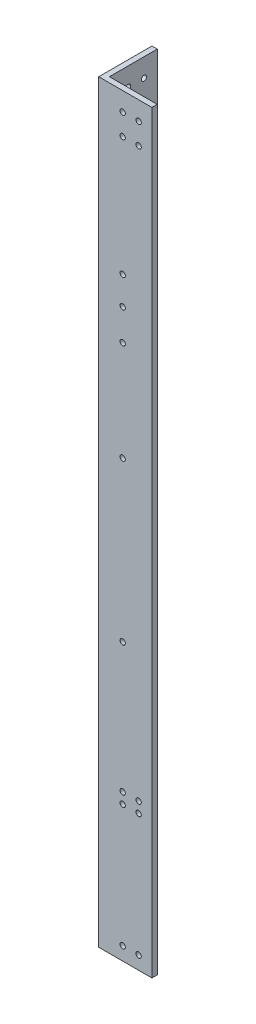
SolidWorks part; units mm, degrees
ref_plane "Front Plane" through (0, 0, 0) normal (0, 0, 1) x (1, 0, 0)
ref_plane "Top Plane" through (0, 0, 0) normal (0, 1, 0) x (1, 0, 0)
ref_plane "Right Plane" through (0, 0, 0) normal (1, 0, 0) x (0, 0, -1)
sketch "Sketch2" plane through (0, 0, 0) normal (0, 1, 0) x (1, 0, 0)
  line L0 (0, 31.75) -> (3.175, 31.75)
  line L1 (3.175, 31.75) -> (3.175, 3.175)
  line L2 (3.175, 3.175) -> (31.75, 3.175)
  line L3 (31.75, 3.175) -> (31.75, 0)
  line L4 (31.75, 0) -> (0, 0)
  line L5 (0, 0) -> (0, 31.75)
  point P9 (1.5875, 31.75)
  point P10 (31.75, 1.5875)
  dimension "D4" = 3.175
  dimension "D1" = 31.75
  dimension "D2" = 31.75
  dimension "D3" = 3.175
extrude "Boss-Extrude1" add sketch "Sketch2" along normal blind 450
sketch "FrontSideHoles-Sketch3" plane through (0, 0, 0) normal (0, 0, 1) x (1, 0, 0)
  line L0 (0, 0) -> (31.75, 0) construction
  line L3 (0, 450) -> (0, 0) construction
  circle A0 centre (14.2875, 81.1125) radius 1.5875
  circle A1 centre (23.8125, 81.1125) radius 1.5875
  circle A2 centre (14.2875, 87.4625) radius 1.5875
  circle A3 centre (23.8125, 87.4625) radius 1.5875
  circle A4 centre (14.2875, 438.8875) radius 1.5875
  circle A5 centre (14.2875, 426.1875) radius 1.5875
  circle A6 centre (23.8125, 438.8875) radius 1.5875
  circle A7 centre (23.8125, 426.1875) radius 1.5875
  circle A8 centre (14.2875, 338.1776) radius 1.5875
  circle A9 centre (14.2875, 319.6526) radius 1.5875
  circle A10 centre (14.2875, 260) radius 1.5875
  circle A11 centre (14.2875, 165) radius 1.5875
  circle A12 centre (14.2875, 355) radius 1.5875
  circle A13 centre (14.2875, 7.9375) radius 1.5875
  circle A14 centre (23.8125, 7.9375) radius 1.5875
  dimension "D4" = 3.175
  dimension "D1" = 81.1125
  dimension "D2" = 14.2875
  dimension "D8" = 11.1125
  dimension "D11" = 18.525
  dimension "D5" = 6.35
  dimension "D3" = 9.525
  dimension "D7" = 12.7
  dimension "D9" = 319.6526
  dimension "D6" = 165
  dimension "D10" = 95
  dimension "D13" = 95
  dimension "D12" = 7.9375
sketch "LeftSideHoles-Sketch4" plane through (0, 0, 0) normal (-1, 0, 0) x (0, 0, 1)
  line L0 (-31.75, 450) -> (0, 450) construction
  line L1 (0, 450) -> (0, 0) construction
  line L3 (-31.75, 0) -> (0, 0) construction
  circle A0 centre (-23.8125, 81.1125) radius 1.5875
  circle A1 centre (-14.2875, 81.1125) radius 1.5875
  circle A2 centre (-23.8125, 87.4625) radius 1.5875
  circle A3 centre (-14.2875, 87.4625) radius 1.5875
  circle A4 centre (-23.8125, 438.8875) radius 1.5875
  circle A5 centre (-14.2875, 438.8875) radius 1.5875
  circle A6 centre (-23.8125, 426.1875) radius 1.5875
  circle A7 centre (-14.2875, 426.1875) radius 1.5875
  circle A8 centre (-23.8125, 332.6026) radius 1.5875
  circle A9 centre (-14.2875, 332.6026) radius 1.5875
  circle A10 centre (-23.8125, 319.9026) radius 1.5875
  circle A11 centre (-14.2875, 319.9026) radius 1.5875
  circle A12 centre (-23.8125, 7.9375) radius 1.5875
  circle A13 centre (-14.2875, 7.9375) radius 1.5875
  circle A14 centre (-14.2875, 165) radius 7.0254
  circle A15 centre (-14.2875, 260) radius 7.1716
  circle A16 centre (-14.2875, 355) radius 6.6199
  dimension "D4" = 3.175
  dimension "D2" = 14.2875
  dimension "D7" = 12.7
  dimension "D13" = 95
  dimension "D3" = 81.1125
  dimension "D6" = 11.1125
  dimension "D5" = 6.35
  dimension "D10" = 7.9375
  dimension "D9" = 12.7
  dimension "D11" = 9.525
  dimension "D8" = 332.6026
  dimension "D12" = 165
  dimension "D14" = 95
extrude "FrontSideHoles-Cut-Extrude1" cut sketch "FrontSideHoles-Sketch3" against normal blind 3.175
extrude "LeftSideHoles-Cut-Extrude2" cut sketch "LeftSideHoles-Sketch4" against normal blind 3.175
equation "\"RailThickness\"= .125in'Spec"
equation "\"VSWidth\"= 1.25in'Spec"
equation "\"VSHeight\"= 1.25in'Spec"
equation "\"VSLength\"= 450mm"
equation "\"HoleOffsetFromEdge\"= \"RailThickness\" * 2.5"
equation "\"HoleOffsetFromSide\"= \"RailThickness\" * 3.5"
equation "\"LegHeight\"= 70mm'Space needed for PSU/Stepper/Electronics"
equation "\"VSBottomSideRailHoleY1FromBottomOfLowerRail\"= \"V1 BottomOfLowerRail\" + \"HoleOffsetFromSide\"'Equals 70.1125"
equation "\"VSSideRailHoleX1FromSide\"= \"HoleOffsetFromSide\" + \"RailThickness\""
equation "\"FasteningHoleDiameter\"= .125in"
equation "\"VSBottomSideRailHoleY2FromY1\"= \"LowerRailHeight\" - \"HoleOffsetFromSide\" - \"HoleOffsetFromEdge\"'Equals 6.35"
equation "\"VSTopSideRailHoleY1FromEdge\"= \"HoleOffsetFromEdge\" + \"RailThickness\""
equation "\"D4@FrontSideHoles-Sketch3\" = \"FasteningHoleDiameter\""
equation "\"D1@FrontSideHoles-Sketch3\" = \"VSBottomSideRailHoleY1FromBottomOfLowerRail\""
equation "\"D2@FrontSideHoles-Sketch3\" = \"VSSideRailHoleX1FromSide\""
equation "\"D1@Boss-Extrude1\"=\"VSLength\""
equation "\"D4@LeftSideHoles-Sketch4\" = \"FasteningHoleDiameter\""
equation "\"D3@LeftSideHoles-Sketch4\"= \"VSBottomSideRailHoleY1FromBottomOfLowerRail\""
equation "\"D2@LeftSideHoles-Sketch4\" = \"VSSideRailHoleX1FromSide\""
equation "\"D8@FrontSideHoles-Sketch3\" = \"VSTopSideRailHoleY1FromEdge\""
equation "\"D6@LeftSideHoles-Sketch4\" = \"VSTopSideRailHoleY1FromEdge\""
equation "\"VSMidSideRailHoleY1FromV8TopOfMidSideRail\"= \"V8 ToTopOfMidSideRail\" - \"HoleOffsetFromEdge\"'Equals 308.2875"
equation "\"LowerRailHeight\"= 1.00in"
equation "\"D1@Sketch2\"=\"VSHeight\""
equation "\"D2@Sketch2\"=\"VSWidth\""
equation "\"TopRailHeight\"= 1.25in"
equation "\"MidSideRailHeight\"= 1.25in"
equation "\"D5@LeftSideHoles-Sketch4\"=\"VSBottomSideRailHoleY2FromY1\""
equation "\"D5@FrontSideHoles-Sketch3\"=\"VSBottomSideRailHoleY2FromY1\""
equation "\"D10@LeftSideHoles-Sketch4\"=\"HoleOffsetFromEdge\""
equation "\"VSMidSideRailHoleY2FromY1\"= \"MidSideRailHeight\" - \"HoleOffsetFromSide\" - \"HoleOffsetFromEdge\"'Equals 12.7"
equation "\"D9@LeftSideHoles-Sketch4\"=\"VSMidSideRailHoleY2FromY1\""
equation "\"VSSideRailHoleX2FromX1\"= \"VSWidth\" - \"VSSideRailHoleX1FromSide\" - \"HoleOffsetFromEdge\""
equation "\"D3@FrontSideHoles-Sketch3\"=\"VSSideRailHoleX2FromX1\""
equation "\"D7@FrontSideHoles-Sketch3\"=\"VSMidSideRailHoleY2FromY1\""
equation "\"D11@LeftSideHoles-Sketch4\"=\"VSSideRailHoleX2FromX1\""
equation "\"VSTopSideRailHoleY2FromY1\"= \"TopRailHeight\" - \"VSTopSideRailHoleY1FromEdge\" - \"HoleOffsetFromEdge\"'Equals 12.7"
equation "\"D7@LeftSideHoles-Sketch4\"=\"VSTopSideRailHoleY2FromY1\""
equation "\"BeltTensionerInnerHeight\"= \"20TGT2PulleyWidth\" * 2 + \"1mmSpacer\" * 3"
equation "\"20TGT2PulleyWidth\"= 8.7mm'The STL of the Pulley in the diagram is a bit larger"
equation "\"1mmSpacer\"= 1mm"
equation "\"BeltTensionerHeight\"= \"BeltTensionerInnerHeight\" + \"BeltTensionerUpperLowerWallThickness\" * 2"
equation "\"BeltTensionerUpperLowerWallThickness\"= 7mm"
equation "\"D11@FrontSideHoles-Sketch3\"=\"VSBeltTensionerHoleY2FromY1\""
equation "\"VSBeltTensionerHoleY1FromBottom\"= \"V9 FromBottomGantryPulleyToBottomOfBeltTensioner\" + \"HoleOffsetFromEdge\""
equation "\"VSBeltTensionerHoleY2FromY1\"= \"BeltTensionerHeight\" - \"HoleOffsetFromEdge\" * 2"
equation "\"V1 BottomOfLowerRail\"= \"LegHeight\""
equation "\"StepperShaftLength\"= 24mm'Pulley will be attached to the end"
equation "\"ZAxisLeadScrewLength\"= 200mm"
equation "\"LM8UUHeight\"= 24mm'Spec"
equation "\"V2 ToBedAtTopOfZAxis\"= \"V1 BottomOfLowerRail\" + \"StepperShaftLength\" + \"ZAxisLeadScrewLength\" - \"LM8UUHeight\" / 2"
equation "\"HotEndToTopOfXAxisGB\"= 63.315144mm'Measured from the100.Should be 63.315144"
equation "\"TopOfGBToBottomOfLinearRail\"= \"LinearGBWidth\" / 2 + \"LinearRailWidth\" / 2"
equation "\"LinearGBWidth\"= 27mm'Spec"
equation "\"V5 ToBottomOfXAxisLinearRail\"= \"V4 ToTopOfBuildPlate/HotEndTip\" + \"HotEndToTopOfXAxisGB\" - \"TopOfGBToBottomOfLinearRail\""
equation "\"LinearRailWidth\"= 12mm'Spec"
equation "\"V6 ToBottomOfGantryPulley\"= \"V5 ToBottomOfXAxisLinearRail\" - \"DistanceFromGABTopToLowerPulley\""
equation "\"GABUpperHeight\"= 6mm"
equation "\"GABMidWallHeight\"= 28mm'Must equal 28 or changes alignment"
equation "\"GABMidShortRiserHeight\"= \"GABMidWallHeight\" / 2 - \"20TGT2PulleyWidth\"'Equals 5.3"
equation "\"GABRiserBossOffset\"= 0.8mm'Aligns Pulleys"
equation "\"DistanceFromGABTopToLowerPulley\"= \"GABUpperHeight\" + \"GABMidWallHeight\" - \"GABMidShortRiserHeight\" + \"GABRiserBossOffset\" / 2"
equation "\"V7 ToTopOfMidBackRail\"= \"V6 ToBottomOfGantryPulley\" + \"StepperShaftLength\""
equation "\"D8@LeftSideHoles-Sketch4\"= \"VSMidSideRailHoleY1FromV8TopOfMidSideRail\""
equation "\"BedToBuildPlateStandoffLength\"= 15mm"
equation "\"BuildPlateHeight\"= 8mm'Spec"
equation "\"V4 ToTopOfBuildPlate/HotEndTip\"= \"V2 ToBedAtTopOfZAxis\" + \"BedToBuildPlateStandoffLength\" + \"BuildPlateHeight\""
equation "\"D9@FrontSideHoles-Sketch3\"=\"VSBeltTensionerHoleY1FromBottom\""
equation "\"V8 ToTopOfMidSideRail\"= \"V7 ToTopOfMidBackRail\" - \"RailThickness\""
equation "\"V9 FromBottomGantryPulleyToBottomOfBeltTensioner\"= \"V6 ToBottomOfGantryPulley\" - \"BeltTensionerUpperLowerWallThickness\" - \"1mmSpacer\""
equation "\"BeltTensionerMountingHoleOffsetFromEdge\"= \"HoleOffsetFromEdge\""
equation "\"VSBeltTensionerXMountingHoleOffsetFromSide\"= \"BeltTensionerMountingHoleOffsetFromEdge\" + \"RailThickness\" * 2"
equation "\"VSEnclosureOffsets\"= ( \"VSLength\" - \"LegHeight\" ) / 4"
equation "\"D6@FrontSideHoles-Sketch3\"=\"LegHeight\" + \"VSEnclosureOffsets\""
equation "\"D10@FrontSideHoles-Sketch3\"=\"VSEnclosureOffsets\""
equation "\"D13@FrontSideHoles-Sketch3\"=\"VSEnclosureOffsets\""
equation "\"D12@FrontSideHoles-Sketch3\"=\"HoleOffsetFromEdge\""
equation "\"D13@LeftSideHoles-Sketch4\"=\"VSEnclosureOffsets\""
equation "\"D14@LeftSideHoles-Sketch4\"=\"VSEnclosureOffsets\""
equation "\"D12@LeftSideHoles-Sketch4\"=\"LegHeight\" + \"VSEnclosureOffsets\""
